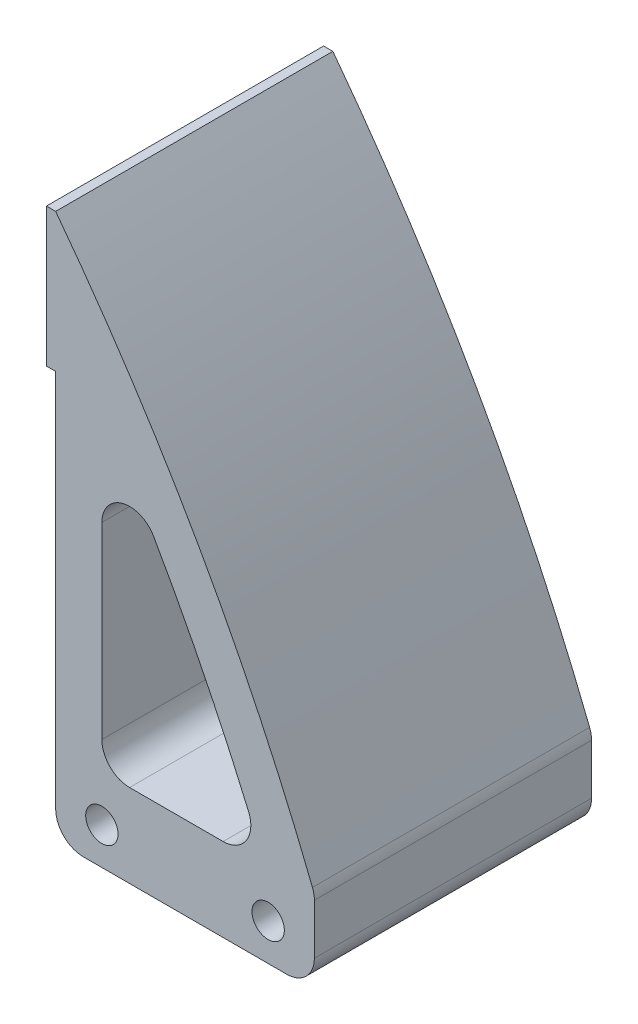
SolidWorks part; units mm, degrees
ref_plane "前视基准面" through (0, 0, 0) normal (0, 0, 1) x (1, 0, 0)
ref_plane "上视基准面" through (0, 0, 0) normal (0, 1, 0) x (1, 0, 0)
ref_plane "右视基准面" through (0, 0, 0) normal (1, 0, 0) x (0, 0, -1)
other "Configuration Table"
sketch "草图1" plane through (0, 0, 0) normal (0, 0, 1) x (1, 0, 0)
  line L0 (0, 6) -> (0, -6) construction
  line L1 (-14, 6) -> (14, 6)
  line L2 (-14, 6) -> (-14, -6)
  line L3 (-14, -6) -> (14, -6)
  line L4 (14, 6) -> (14, -6)
  line L5 (-14, 6) -> (14, -6) construction
  line L6 (-14, -6) -> (14, 6) construction
  line L7 (-14, 6) -> (-14, 56)
  line L8 (-9, 6) -> (-9, 40.0975)
  line L10 (-14, 56) -> (-15, 56)
  line L11 (-14, 56) -> (-14, 41)
  line L12 (-14, 41) -> (-15, 41)
  line L13 (-15, 56) -> (-15, 41)
  circle A0 centre (-9, 1) radius 1.75
  circle A1 centre (9, 1) radius 1.75
  arc A2 (-14, 56) -> (14, 6) centre (-181.5127, -70.6471) cw
  arc A3 (-9, 40.0975) -> (8.6194, 6) centre (-181.5127, -70.6471) cw
  arc A4 (-9, 40.0975) -> (9.3449, 4.1751) centre (-181.5127, -70.6471) cw construction
  point P0 (0, 0)
  point P18 (8.6194, 6)
  dimension "D2" = 3.5
  dimension "D7" = 210
  dimension "D1" = 12
  dimension "D3" = 5
  dimension "D4" = 5
  dimension "D5" = 28
  dimension "D6" = 50
  dimension "D9" = 1
  dimension "D10" = 15
  dimension "D8" = 5
extrude "凸台-拉伸1" add sketch "草图1" along normal blind 30 contours L8 A3 L1 A2 L7 | L10 L13 L12 L7 | L4 L1 L2 L3 A0 A1 region at (-13.4269, 23.5, 0) region at (0, -0.0607, 0) region at (-14.5, 48.5, 0)
fillet "圆角1" radius 3 5 edges at (14, -6, 15) (-14, -6, 15) (8.6194, 6, 15) (-9, 40.0975, 15) (-9, 6, 15)
sketch "草图2" plane through (0, 0, 30) normal (0, 0, 1) x (1, 0, 0)
  line L0 (-14, -3) -> (14, -3)
  line L6 (-11, -6) -> (11, -6)
  line L7 (14, -3) -> (14, 6)
  line L8 (-14, 56) -> (-15, 56)
  line L9 (-15, 56) -> (-15, 41)
  line L10 (-15, 41) -> (-14, 41)
  line L11 (-14, 41) -> (-14, -3)
  line L12 (-11, -6) -> (11, -6)
  line L13 (14, -3) -> (14, 6)
  line L14 (-14, 56) -> (-15, 56)
  line L15 (-15, 56) -> (-15, 41)
  line L16 (-15, 41) -> (-14, 41)
  line L17 (-14, 41) -> (-14, -3)
  arc A3 (11, -6) -> (14, -3) centre (11, -3) ccw
  arc A4 (14, 6) -> (-14, 56) centre (-181.5127, -70.6471) ccw
  arc A5 (-14, -3) -> (-11, -6) centre (-11, -3) ccw
  arc A6 (11, -6) -> (14, -3) centre (11, -3) ccw
  arc A7 (14, 6) -> (-14, 56) centre (-181.5127, -70.6471) ccw
  arc A8 (-14, -3) -> (-11, -6) centre (-11, -3) ccw
  line M11 (-11, -6) -> (11, -6)
  arc M12 (11, -6) -> (14, -3) centre (11, -3) ccw
  arc M19 (-14, -3) -> (-11, -6) centre (-11, -3) ccw
  dimension "D2" = 3
  dimension "D1" = 0
extrude "切除-拉伸1" cut sketch "草图2" against normal through all contours L0 M19 M11 M12 region at (0, -4.46, 30)
fillet "圆角2" radius 3 3 edges at (14, -3, 15) (14, 6, 15) (-14, -3, 15)
sketch "草图3" plane through (0, 0, 0) normal (0, 0, -1) x (-1, 0, 0)
  circle A0 centre (-9, 1) radius 1.75 construction
  circle A1 centre (9, 1) radius 1.75 construction
  circle A2 centre (-9, 1) radius 1.75
  circle A3 centre (9, 1) radius 1.75
extrude "凸台-拉伸2" add sketch "草图3" against normal offset from surface (23.5 mm away) 6.5 up to face at (-2.6946, 15.3842, 30)
sketch "草图4" plane through (0, 0, 0) normal (0, 0, -1) x (-1, 0, 0)
  circle A0 centre (-9, 1) radius 1.75 construction
  circle A1 centre (9, 1) radius 1.75 construction
  circle A2 centre (-9, 1) radius 1.75
  circle A3 centre (9, 1) radius 1.75
extrude "切除-拉伸2" cut sketch "草图4" against normal blind 6.5
